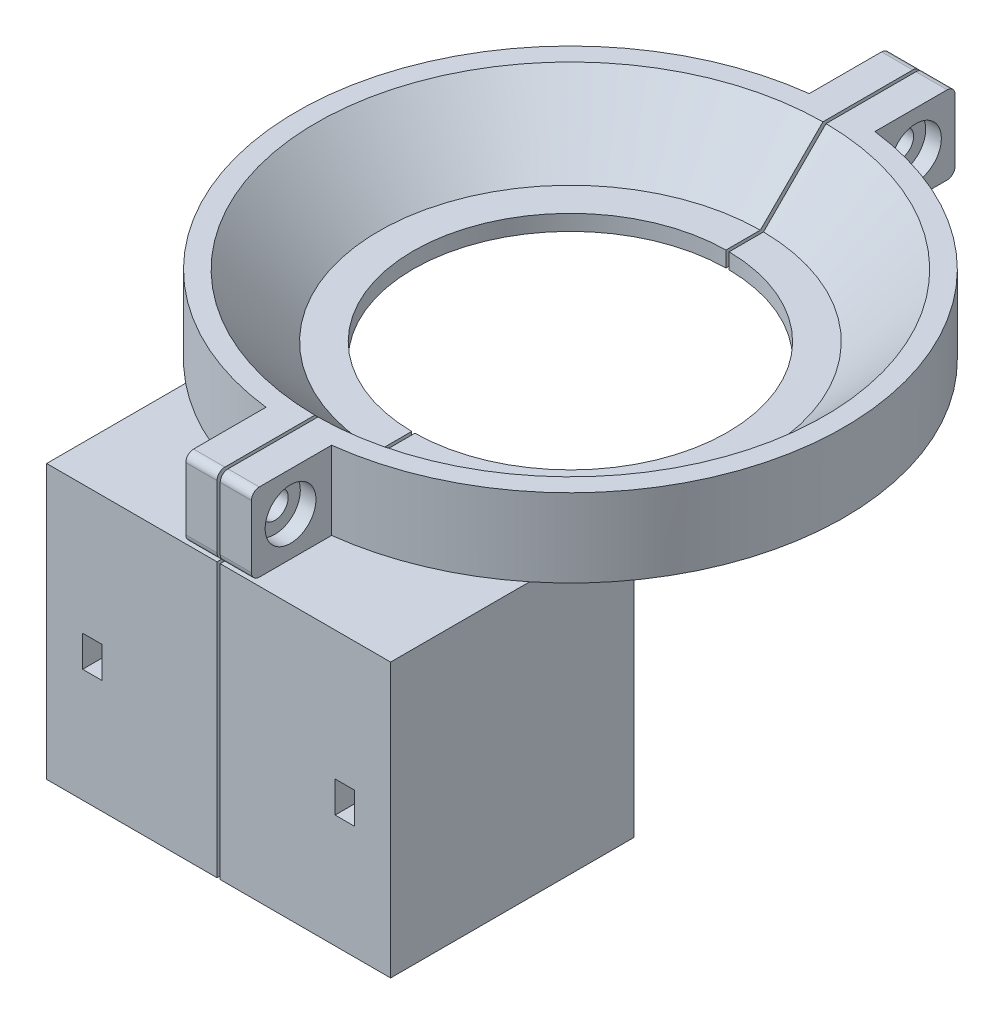
SolidWorks part; units mm, degrees
ref_plane "Front Plane" through (0, 0, 0) normal (0, 0, 1) x (1, 0, 0)
ref_plane "Top Plane" through (0, 0, 0) normal (0, 1, 0) x (1, 0, 0)
ref_plane "Right Plane" through (0, 0, 0) normal (1, 0, 0) x (0, 0, -1)
sketch "Croquis1" plane through (0, 0, 0) normal (0, 1, 0) x (1, 0, 0)
  line L0 (-22.5, 0) -> (22.5, 0) construction
  line L1 (0, 22.5) -> (0, -22.5) construction
  line L2 (-22.5, 0) -> (-20.1, 0)
  line L3 (0, -20.1) -> (0, -22.5)
  arc A0 (-20.1, 0) -> (0, -20.1) centre (0, 0) ccw
  arc A1 (-22.5, 0) -> (0, -22.5) centre (0, 0) ccw
  dimension "D1" = 40.2
  dimension "D2" = 45
extrude "Saliente-Extruir1" add sketch "Croquis1" along normal blind 2
sketch "Croquis6" plane through (0, 0, 0) normal (0, 1, 0) x (1, 0, 0)
  line L0 (-35, 0) -> (-22.5, 0)
  line L1 (-35, 0) -> (-22.5, 0) construction
  line L2 (0, -22.5) -> (0, -35) construction
  line L3 (0, -22.5) -> (0, -35)
  arc A0 (-35, 0) -> (0, -35) centre (0, 0) ccw
  arc A1 (-22.5, 0) -> (0, -22.5) centre (0, 0) ccw
  dimension "D1" = 70
extrude "Saliente-Extruir3" add sketch "Croquis6" along normal blind 10
chamfer "Chaflán1" distance 10 angle 45 1 edges at (-15.9099, 10, 15.9099)
ref_plane "Plano1" through (0, 0, 35) normal (0, 0, 1) x (1, 0, 0)
sketch "Croquis8" plane through (0, 0, 35) normal (0, 0, 1) x (1, 0, 0)
  line L0 (-35, 0) -> (0, 0) construction
  line L1 (0, 10) -> (-0.2, 10)
  line L2 (0, 10) -> (0, 0)
  line L3 (0, 0) -> (-0.2, 0)
  line L4 (-0.2, 10) -> (-0.2, 0)
  dimension "D1" = 0.2
extrude "Cortar-Extruir3" cut sketch "Croquis8" against normal through all
sketch "Croquis9" plane through (0, 0, 35) normal (0, 0, 1) x (1, 0, 0)
  line L0 (-35, 0) -> (-0.2, 0) construction
  line L1 (-0.2, 10) -> (-4.2, 10)
  line L2 (-0.2, 10) -> (-0.2, 0)
  line L3 (-0.2, 0) -> (-4.2, 0)
  line L4 (-4.2, 10) -> (-4.2, 0)
  dimension "D1" = 4
extrude "Saliente-Extruir5" add sketch "Croquis9" along normal blind 10 and the other way up to next
fillet "Redondeo4" radius 1 2 edges at (-2.2, 0, 45) (-2.2, 10, 45)
mirror "Simetría30" about plane through (0, 0, 0) normal (0, 0, 1) of bodies 116
sketch "Croquis11" plane through (0, 0, 35) normal (0, 0, 1) x (1, 0, 0)
  line L1 (-0.2, 0) -> (-22, 0)
  line L2 (-0.2, 0) -> (-0.2, -35)
  line L3 (-0.2, -35) -> (-22, -35)
  line L4 (-22, 0) -> (-22, -35)
  dimension "D1" = 35
  dimension "D2" = 21.8
extrude "Saliente-Extruir7" add sketch "Croquis11" along normal up to surface (10 mm away) up to face at (-2.2, 5, 45)
sketch "Croquis12" plane through (0, 0, 0) normal (0, -1, 0) x (1, 0, 0)
  line L0 (-0.2, 35) -> (-0.2, 25.9992)
  line L1 (-0.2, 35) -> (-22, 35)
  line L2 (-22, 35) -> (-22, 27.2213)
  line L3 (-22, 27.2213) -> (-22, 13.8564)
  line L5 (-0.2, 20.099) -> (-0.2, 35) construction
  arc A1 (-4.2, 34.7471) -> (-4.2, -34.7471) centre (0, 0) ccw construction
  arc A2 (-0.2, 25.9992) -> (-22, 13.8564) centre (0, 0) ccw
  dimension "D1" = 26
extrude "Saliente-Extruir8" add sketch "Croquis12" along normal up to surface (35 mm away) up to face at (-11.1, -35, 40)
sketch "Croquis13" plane through (0, 0, 45) normal (0, 0, 1) x (1, 0, 0)
  line L0 (-0.2, 0) -> (-0.2, -35) construction
  line L1 (-14.9, -16.5) -> (-17.4, -16.5)
  line L2 (-14.9, -16.5) -> (-14.9, -20.5)
  line L3 (-14.9, -20.5) -> (-17.4, -20.5)
  line L4 (-17.4, -16.5) -> (-17.4, -20.5)
  line L5 (-4.2, 0) -> (-22, 0) construction
  dimension "D1" = 16.5
  dimension "D2" = 4
  dimension "D3" = 2.5
  dimension "D4" = 17.2
extrude "Cortar-Extruir4" cut sketch "Croquis13" against normal through all
mirror "Simetría32" about plane through (0, 0, 0) normal (1, 0, 0) of bodies 123
hole_wizard "Refrentado para tornillo con cabeza plana de M31" positions "Croquis16" profile "Croquis15" counterbore size "M3" standard "DIN" end condition through all
sketch "Croquis16" plane through (4.2, 0, 0) normal (1, 0, 0) x (0, 0, -1)
  line L0 (-34.7471, 10) -> (-44, 10) construction
  line L2 (-45, 9) -> (-45, 1) construction
  line L7 (45, 9) -> (45, 1) construction
  line L8 (34.7471, 10) -> (44, 10) construction
  point P0 (-40, 5)
  point P2 (40, 5)
  dimension "D2" = 5
  dimension "D1" = 5
  dimension "D3" = 5
  dimension "D4" = 5
sketch "Croquis15" plane through (4.2, 5, 40) normal (0, 1, 0) x (0, 0, -1)
  line L0 (0, 0) -> (0, 39.2)
  line L1 (0, 39.2) -> (1.7, 39.2)
  line L3 (1.7, 39.2) -> (1.7, 2)
  line L4 (1.7, 2) -> (3.25, 2)
  line L5 (3.25, 2) -> (3.25, 0)
  line L7 (3.25, 0) -> (0, 0)
  line L11 (0, -6.35) -> (0, 107.95) construction
  dimension "Diámetro de taladro hasta el siguiente" = 3.4
  dimension "Profundidad de taladro hasta el siguiente" = 39.2
  dimension "Diámetro de refrentado" = 6.5
  dimension "Profundidad de refrentado" = 2
sketch "Croquis17" plane through (-4.2, 0, 0) normal (-1, 0, 0) x (0, 0, 1)
  line L1 (40, 8.4064) -> (37.05, 6.7032)
  line L2 (37.05, 6.7032) -> (37.05, 3.2968)
  line L3 (37.05, 3.2968) -> (40, 1.5936)
  line L4 (40, 1.5936) -> (42.95, 3.2968)
  line L5 (42.95, 3.2968) -> (42.95, 6.7032)
  line L6 (42.95, 6.7032) -> (40, 8.4064)
  circle A0 centre (40, 5) radius 2.95 construction
  dimension "D1" = 5.9
extrude "Cortar-Extruir5" cut sketch "Croquis17" against normal blind 2
mirror "Simetría33" about plane through (0, 0, 0) normal (0, 0, 1) of "Cortar-Extruir5"
